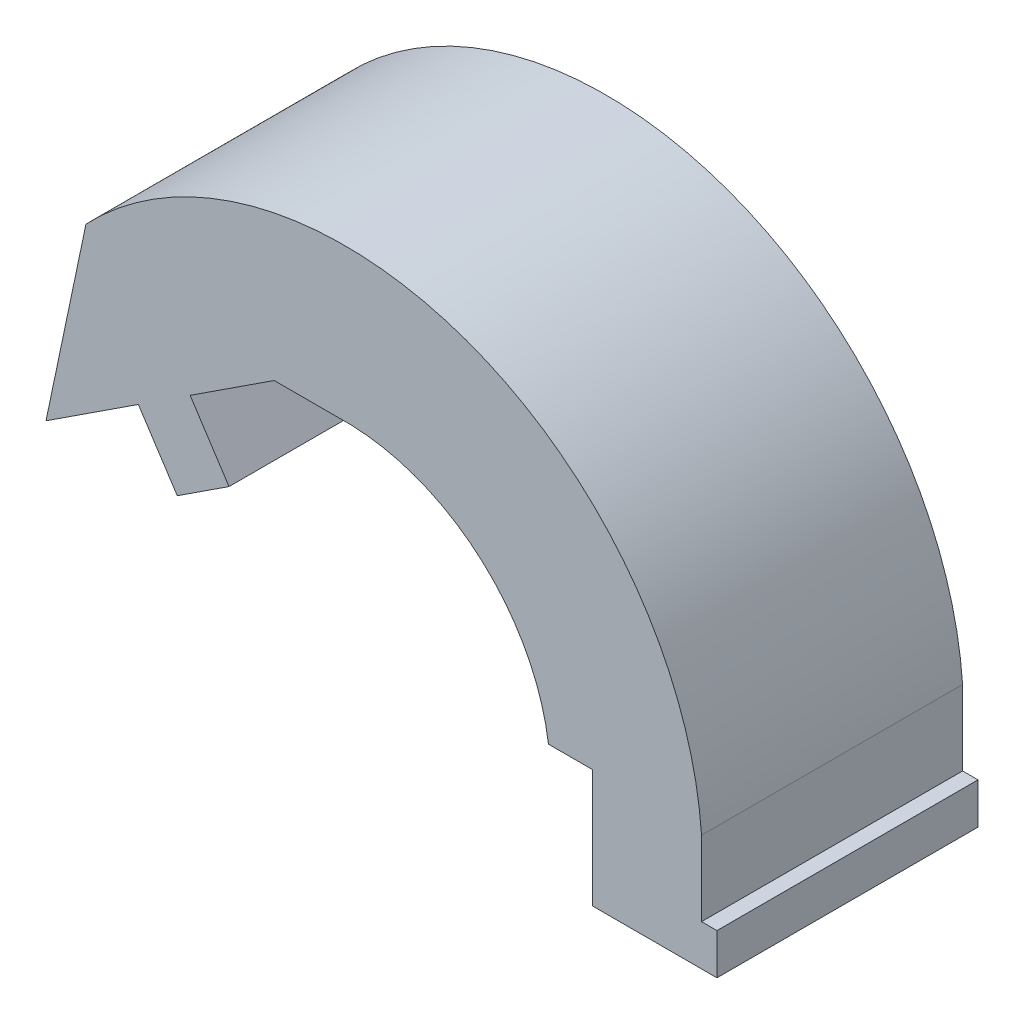
SolidWorks part; units mm, degrees
ref_plane "Front Plane" through (0, 0, 0) normal (0, 0, 1) x (1, 0, 0)
ref_plane "Top Plane" through (0, 0, 0) normal (0, 1, 0) x (1, 0, 0)
ref_plane "Right Plane" through (0, 0, 0) normal (1, 0, 0) x (0, 0, -1)
sketch "Sketch3" plane through (0, 0, 0) normal (0, 0, 1) x (1, 0, 0)
  line L0 (-39.0058, 10.5312) -> (-39.2185, 10.3924)
  line L3 (-36.2747, 12.3143) -> (-36.4874, 12.1754)
  line L8 (-43.4994, 7.5974) -> (-39.2185, 10.3924) construction
  line L17 (-17.1709, 0.1948) -> (-17.1709, 6.1948) construction
  line L36 (-32.3988, 14.8448) -> (-28.6488, 14.8448) construction
  line L37 (-36.2747, 12.3143) -> (-34.2434, 9.203) construction
  line L39 (-43.4994, 7.5974) -> (-41.5545, 16.8586)
  line L51 (-17.1709, 0.1948) -> (-11.4125, 0.1948) construction
  line L52 (-11.3528, 5.1546) -> (-11.3528, 2.6948) construction
  line L57 (-34.2434, 9.203) -> (-37.1871, 7.281) construction
  line L58 (-11.4125, 0.1948) -> (-10.6028, 0.1948) construction
  line L60 (-11.3528, 2.6948) -> (-10.6028, 2.6948) construction
  line L61 (-10.6028, 0.1948) -> (-10.6028, 2.6948) construction
  line L62 (-37.1871, 7.281) -> (-39.2185, 10.3924) construction
  line L63 (-36.2747, 12.3143) -> (-32.3988, 14.8448) construction
  line L64 (-11.6068, 5.1546) -> (-11.6068, 2.4408)
  line L65 (-11.6068, 2.4408) -> (-10.8568, 2.4408)
  line L66 (-10.8568, 2.4408) -> (-10.8568, 0.4488)
  line L67 (-10.8568, 0.4488) -> (-16.9169, 0.4488)
  line L68 (-16.9169, 0.4488) -> (-16.9169, 6.1948)
  line L69 (-36.4874, 12.1754) -> (-34.5949, 9.2768)
  line L70 (-34.5949, 9.2768) -> (-37.1133, 7.6326)
  line L71 (-37.1133, 7.6326) -> (-39.0058, 10.5312)
  line L72 (-11.6068, 5.1546) -> (-11.6068, 6.0847)
  line L73 (-19.0538, 6.1948) -> (-16.9169, 6.1948)
  line L82 (-36.2747, 12.3143) -> (-34.2434, 9.203)
  line L83 (-34.2434, 9.203) -> (-37.1871, 7.281)
  line L84 (-37.1871, 7.281) -> (-39.2185, 10.3924)
  line L85 (-39.2185, 10.3924) -> (-43.4994, 7.5974)
  line L86 (-16.5246, -6.5052) -> (-0.3986, -6.5052)
  line L87 (-0.3986, -6.5052) -> (-0.3986, 6.1948)
  line L88 (-0.3986, 6.1948) -> (-11.3528, 6.1948)
  line L89 (-11.3528, 6.1948) -> (-11.3528, 2.6948)
  line L90 (-11.3528, 2.6948) -> (-10.6028, 2.6948)
  line L91 (-10.6028, 2.6948) -> (-10.6028, 0.1948)
  line L92 (-10.6028, 0.1948) -> (-17.1709, 0.1948)
  line L93 (-17.1709, 0.1948) -> (-17.1709, 6.1948)
  line L94 (-17.1709, 6.1948) -> (-20.9367, 6.1948)
  line L95 (-20.9367, 6.1948) -> (-26.0468, -2.6562)
  line L96 (-34.7105, 2.3457) -> (-28.6488, 12.8448)
  line L97 (-28.6488, 12.8448) -> (-28.6488, 14.8448)
  line L98 (-28.6488, 14.8448) -> (-32.3988, 14.8448)
  line L99 (-32.3988, 14.8448) -> (-36.2747, 12.3143)
  line L100 (-36.2747, 12.3143) -> (-34.2434, 9.203) construction
  line L101 (-34.2434, 9.203) -> (-37.1871, 7.281) construction
  line L102 (-37.1871, 7.281) -> (-39.2185, 10.3924) construction
  line L103 (-39.2185, 10.3924) -> (-43.4994, 7.5974)
  line L104 (-16.5246, -6.5052) -> (-0.3986, -6.5052) construction
  line L105 (-0.3986, -6.5052) -> (-0.3986, 6.1948) construction
  line L106 (-0.3986, 6.1948) -> (-11.3528, 6.1948) construction
  line L107 (-11.3528, 6.1948) -> (-11.3528, 2.6948) construction
  line L108 (-11.3528, 2.6948) -> (-10.6028, 2.6948) construction
  line L109 (-10.6028, 2.6948) -> (-10.6028, 0.1948) construction
  line L110 (-10.6028, 0.1948) -> (-17.1709, 0.1948) construction
  line L111 (-17.1709, 0.1948) -> (-17.1709, 6.1948) construction
  line L112 (-17.1709, 6.1948) -> (-20.9367, 6.1948) construction
  line L113 (-20.9367, 6.1948) -> (-26.0468, -2.6562) construction
  line L114 (-34.7105, 2.3457) -> (-28.6488, 12.8448) construction
  line L115 (-28.6488, 12.8448) -> (-28.6488, 14.8448) construction
  line L116 (-28.6488, 14.8448) -> (-32.3988, 14.8448)
  line L117 (-32.3988, 14.8448) -> (-36.2747, 12.3143)
  arc A2 (-28.6488, 14.8448) -> (-19.0538, 6.1948) centre (-28.9629, 4.8497) cw
  arc A9 (-11.6068, 6.0847) -> (-41.5545, 16.8586) centre (-28.9629, 4.8497) ccw
  arc A11 (-43.4994, 7.5974) -> (-16.5246, -6.5052) centre (-30.3786, -0.1552) ccw
  arc A12 (-34.7105, 2.3457) -> (-26.0468, -2.6562) centre (-30.3786, -0.1552) ccw
  arc A13 (-43.4994, 7.5974) -> (-16.5246, -6.5052) centre (-30.3786, -0.1552) ccw construction
  arc A14 (-34.7105, 2.3457) -> (-26.0468, -2.6562) centre (-30.3786, -0.1552) ccw construction
  point P28 (0, 0)
  dimension "D2" = 0
  dimension "D3" = 10
  dimension "D4" = 7.4
  dimension "D1" = 0.254
  dimension "D5" = 45
extrude "Boss-Extrude1" add sketch "Sketch3" against normal blind 12.7
